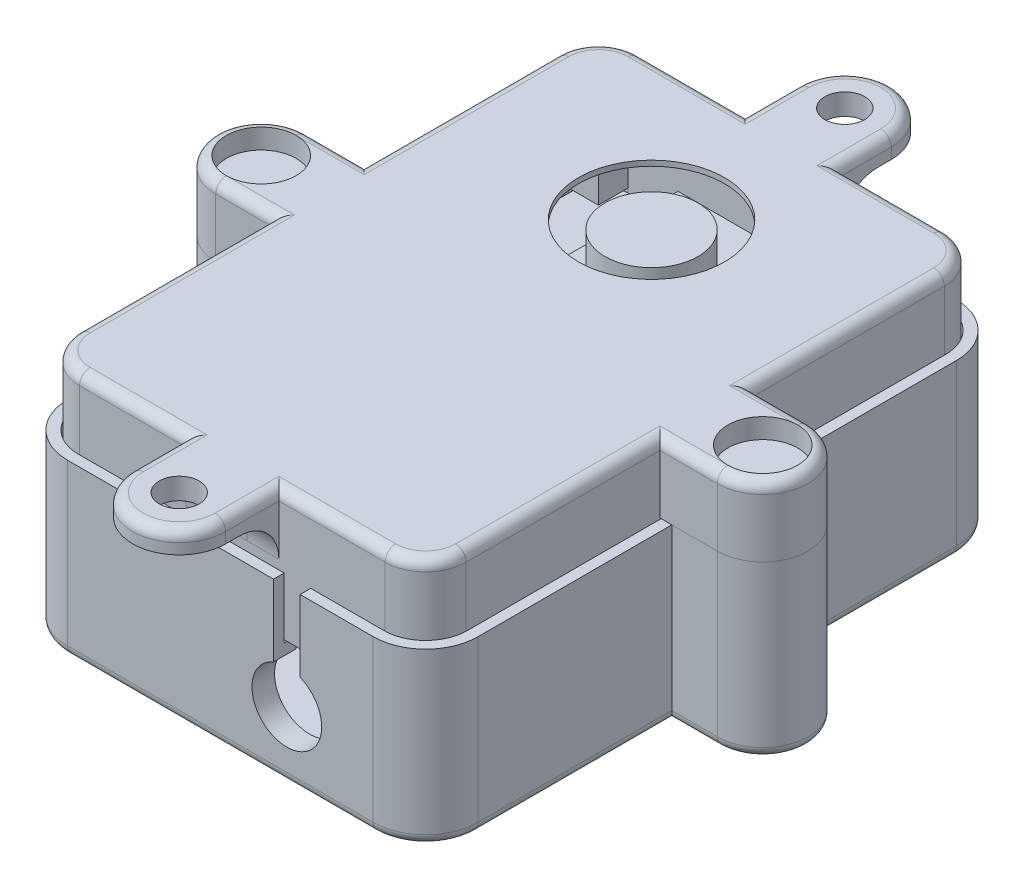
SolidWorks part; units mm, degrees
other "Front Lid"
other "ESP32 Cam"
other "Rear Lid"
ref_plane "Front Plane" through (0, 0, 0) normal (0, 0, 1) x (1, 0, 0)
ref_plane "Top Plane" through (0, 0, 0) normal (0, 1, 0) x (1, 0, 0)
ref_plane "Right Plane" through (0, 0, 0) normal (1, 0, 0) x (0, 0, -1)
sketch "Sketch1" plane through (0, 0, 0) normal (0, 1, 0) x (1, 0, 0)
  line L1 (-11.5, 20) -> (11.5, 20)
  line L2 (-13.5, 18) -> (-13.5, -18)
  line L3 (-11.5, -20) -> (11.5, -20)
  line L4 (13.5, 18) -> (13.5, -18)
  line L5 (-13.5, 20) -> (13.5, -20) construction
  line L6 (-13.5, -20) -> (13.5, 20) construction
  arc A0 (-11.5, 20) -> (-13.5, 18) centre (-11.5, 18) ccw
  arc A1 (11.5, 20) -> (13.5, 18) centre (11.5, 18) cw
  arc A2 (11.5, -20) -> (13.5, -18) centre (11.5, -18) ccw
  arc A3 (-13.5, -18) -> (-11.5, -20) centre (-11.5, -18) ccw
  point P0 (0, 0)
  dimension "D3" = 2
  dimension "D1" = 27
  dimension "D2" = 40
extrude "Boss-Extrude1" add sketch "Sketch1" along normal blind 1
sketch "Sketch2" plane through (0, 1, 0) normal (0, 1, 0) x (1, 0, 0)
  line L0 (0, 0) -> (0, 20) construction
  line L1 (11.5, 20) -> (-11.5, 20) construction
  line L3 (-7.5, 20) -> (7.5, 20)
  line L4 (-7.5, 20) -> (-7.5, 5)
  line L5 (-7.5, 5) -> (7.5, 5)
  line L6 (7.5, 20) -> (7.5, 5)
  line L7 (-7.5, 20) -> (7.5, 5) construction
  line L8 (-7.5, 5) -> (7.5, 20) construction
  point P5 (0, 12.5)
  dimension "D1" = 15
extrude "Boss-Extrude2" add sketch "Sketch2" along normal blind 2
sketch "Sketch3" plane through (0, 3, 0) normal (0, 1, 0) x (1, 0, 0)
  line L0 (0, 5) -> (0, 20) construction
  line L1 (-7.5, 5) -> (7.5, 5) construction
  line L2 (7.5, 20) -> (-7.5, 20) construction
  circle A0 centre (0, 10.5) radius 3.5
  dimension "D1" = 7
  dimension "D2" = 5.5
extrude "Lens Position" add sketch "Sketch3" along normal blind 6
sketch "Sketch5" plane through (0, 1, 0) normal (0, 1, 0) x (1, 0, 0)
  line L0 (-11.5, -20) -> (11.5, -20) construction
  line L1 (10, -8) -> (13, -8)
  line L2 (10, -8) -> (10, -11)
  line L3 (10, -11) -> (13, -11)
  line L4 (13, -8) -> (13, -11)
  line L5 (10, -8) -> (13, -11) construction
  line L6 (10, -11) -> (13, -8) construction
  line L7 (13.5, -18) -> (13.5, 18) construction
  point P0 (11.5, -9.5)
  dimension "D1" = 3
  dimension "D2" = 10.5
  dimension "D3" = 2
extrude "Boss-Extrude4" add sketch "Sketch5" along normal blind 1
sketch "Sketch6" plane through (0, 9, 0) normal (0, 1, 0) x (1, 0, 0)
  line L37 (7.5, 21.05) -> (-7.5, 21.05)
  line L38 (-7.5, 21.05) -> (-11.5, 21.05)
  line L39 (-14.55, 18) -> (-14.55, -18)
  line L40 (-11.5, -21.05) -> (11.5, -21.05)
  line L41 (14.55, -18) -> (14.55, 18)
  line L42 (11.5, 21.05) -> (7.5, 21.05)
  line L43 (7.5, 20.25) -> (-7.5, 20.25)
  line L44 (11.5, 20.25) -> (7.5, 20.25)
  line L45 (13.75, -18) -> (13.75, 18)
  line L46 (-11.5, -20.25) -> (11.5, -20.25)
  line L47 (-13.75, 18) -> (-13.75, -18)
  line L48 (-7.5, 20.25) -> (-11.5, 20.25)
  line L55 (7.5, 20.25) -> (-7.5, 20.25) construction
  line L56 (11.5, 20.25) -> (7.5, 20.25) construction
  line L57 (13.75, -18) -> (13.75, 18) construction
  line L58 (-11.5, -20.25) -> (11.5, -20.25) construction
  line L59 (-13.75, 18) -> (-13.75, -18) construction
  line L60 (-7.5, 20.25) -> (-11.5, 20.25) construction
  circle A6 centre (0, 10.5) radius 5.5
  circle A8 centre (0, 10.5) radius 5.5
  arc A36 (-11.5, 21.05) -> (-14.55, 18) centre (-11.5, 18) ccw
  arc A37 (-14.55, -18) -> (-11.5, -21.05) centre (-11.5, -18) ccw
  arc A38 (11.5, -21.05) -> (14.55, -18) centre (11.5, -18) ccw
  arc A39 (14.55, 18) -> (11.5, 21.05) centre (11.5, 18) ccw
  arc A40 (13.75, 18) -> (11.5, 20.25) centre (11.5, 18) ccw
  arc A41 (11.5, -20.25) -> (13.75, -18) centre (11.5, -18) ccw
  arc A42 (-13.75, -18) -> (-11.5, -20.25) centre (-11.5, -18) ccw
  arc A43 (-11.5, 20.25) -> (-13.75, 18) centre (-11.5, 18) ccw
  arc A44 (13.75, 18) -> (11.5, 20.25) centre (11.5, 18) ccw construction
  arc A45 (11.5, -20.25) -> (13.75, -18) centre (11.5, -18) ccw construction
  arc A46 (-13.75, -18) -> (-11.5, -20.25) centre (-11.5, -18) ccw construction
  arc A47 (-11.5, 20.25) -> (-13.75, 18) centre (-11.5, 18) ccw construction
  dimension "D1" = 0.25
  dimension "D2" = 0.8
  dimension "D3" = 2
extrude "Lens Opening" add sketch "Sketch6" along normal blind 0.4 from offset 0.25 separate body
sketch "Sketch8" plane through (0, 9.25, 0) normal (0, -1, 0) x (1, 0, 0)
  line L4 (-11.5, -21.05) -> (11.5, -21.05)
  line L5 (14.55, -18) -> (14.55, 18)
  line L6 (11.5, 21.05) -> (-11.5, 21.05)
  line L7 (-14.55, 18) -> (-14.55, -18)
  line L8 (-11.5, -21.05) -> (11.5, -21.05)
  line L9 (14.55, -18) -> (14.55, 18)
  line L10 (11.5, 21.05) -> (-11.5, 21.05)
  line L11 (-14.55, 18) -> (-14.55, -18)
  line L16 (-11.5, -20.25) -> (11.5, -20.25)
  line L17 (13.75, -18) -> (13.75, 18)
  line L18 (11.5, 20.25) -> (-11.5, 20.25)
  line L19 (-13.75, 18) -> (-13.75, -18)
  line L20 (-11.5, -20.25) -> (11.5, -20.25)
  line L21 (13.75, -18) -> (13.75, 18)
  line L22 (11.5, 20.25) -> (-11.5, 20.25)
  line L23 (-13.75, 18) -> (-13.75, -18)
  arc A4 (11.5, -21.05) -> (14.55, -18) centre (11.5, -18) ccw
  arc A5 (14.55, 18) -> (11.5, 21.05) centre (11.5, 18) ccw
  arc A6 (-11.5, 21.05) -> (-14.55, 18) centre (-11.5, 18) ccw
  arc A7 (-14.55, -18) -> (-11.5, -21.05) centre (-11.5, -18) ccw
  arc A8 (11.5, -21.05) -> (14.55, -18) centre (11.5, -18) ccw
  arc A9 (14.55, 18) -> (11.5, 21.05) centre (11.5, 18) ccw
  arc A10 (-11.5, 21.05) -> (-14.55, 18) centre (-11.5, 18) ccw
  arc A11 (-14.55, -18) -> (-11.5, -21.05) centre (-11.5, -18) ccw
  arc A16 (11.5, -20.25) -> (13.75, -18) centre (11.5, -18) ccw
  arc A17 (13.75, 18) -> (11.5, 20.25) centre (11.5, 18) ccw
  arc A18 (-11.5, 20.25) -> (-13.75, 18) centre (-11.5, 18) ccw
  arc A19 (-13.75, -18) -> (-11.5, -20.25) centre (-11.5, -18) ccw
  arc A20 (11.5, -20.25) -> (13.75, -18) centre (11.5, -18) ccw
  arc A21 (13.75, 18) -> (11.5, 20.25) centre (11.5, 18) ccw
  arc A22 (-11.5, 20.25) -> (-13.75, 18) centre (-11.5, 18) ccw
  arc A23 (-13.75, -18) -> (-11.5, -20.25) centre (-11.5, -18) ccw
  dimension "D1" = 0
  dimension "D2" = 0.8
extrude "Boss-Extrude7" add sketch "Sketch8" along normal up to vertex (9.25 mm away) up to point (-11.5, 0, 20)
sketch "Sketch9" plane through (0, 9.25, 0) normal (0, -1, 0) x (1, 0, 0)
  line L0 (13.75, 18) -> (11.5, 18)
  line L1 (11.5, 18) -> (11.5, 20.25)
  line L2 (4.95, 0) -> (-4.95, 0) construction
  line L3 (11.5, -18) -> (11.5, -20.25)
  line L4 (13.75, -18) -> (11.5, -18)
  line L5 (0, -4.95) -> (0, 4.95) construction
  line L6 (-13.75, -18) -> (-11.5, -18)
  line L7 (-11.5, -18) -> (-11.5, -20.25)
  line L8 (-11.5, 18) -> (-11.5, 20.25)
  line L9 (-13.75, 18) -> (-11.5, 18)
  arc A0 (13.75, 18) -> (11.5, 20.25) centre (11.5, 18) ccw construction
  arc A1 (13.75, 18) -> (11.5, 20.25) centre (11.5, 18) ccw
  arc A2 (13.75, -18) -> (11.5, -20.25) centre (11.5, -18) cw
  arc A3 (-13.75, -18) -> (-11.5, -20.25) centre (-11.5, -18) ccw
  arc A4 (-13.75, 18) -> (-11.5, 20.25) centre (-11.5, 18) cw
extrude "Boss-Extrude9" add sketch "Sketch9" along normal offset from surface (8.15 mm away) 0.1 up to face at (0, 1, -4.1667)
sketch "Sketch11" plane through (0, 9.65, 0) normal (0, 1, 0) x (1, 0, 0)
  line L1 (13.75, -7.6) -> (9.6, -7.6)
  line L2 (9.6, -7.6) -> (9.6, -11.4)
  line L3 (9.6, -11.4) -> (13.75, -11.4)
  line L4 (13, -11) -> (13, -8)
  line L5 (13, -8) -> (10, -8)
  line L6 (10, -8) -> (10, -11)
  line L7 (10, -11) -> (13, -11)
  line L8 (13, -11) -> (13, -8) construction
  line L9 (13, -8) -> (10, -8) construction
  line L10 (10, -8) -> (10, -11) construction
  line L11 (10, -11) -> (13, -11) construction
  line L12 (13.75, 18) -> (13.75, -18) construction
  line L13 (13.75, -7.6) -> (13.75, -11.4)
  line L14 (9.6, -11.4) -> (13.4, -11.4) construction
  line L15 (13.4, -11.4) -> (13.4, -7.6) construction
  line L16 (13.4, -7.6) -> (9.6, -7.6) construction
  dimension "D1" = 0
  dimension "D2" = 0.4
extrude "Cut-Extrude1" [suppressed] cut sketch "Sketch11" against normal up to vertex
sketch "Sketch12" plane through (0, 0, 0) normal (0, -1, 0) x (1, 0, 0)
  line L0 (0, 0) -> (0, 20) construction
  line L1 (-11.5, 20) -> (11.5, 20) construction
  line L3 (9.375, -5.65) -> (-9.375, -5.65)
  line L4 (9.375, -5.65) -> (9.375, 20)
  line L5 (9.375, 20) -> (-9.375, 20)
  line L6 (-9.375, -5.65) -> (-9.375, 20)
  line L7 (9.375, -5.65) -> (-9.375, 20) construction
  line L8 (9.375, 20) -> (-9.375, -5.65) construction
  point P5 (0, 7.175)
  dimension "D1" = 18.75
  dimension "D2" = 25.65
extrude "Boss-Extrude10" add sketch "Sketch12" along normal blind 0.75
sketch "Sketch13" plane through (0, -0.75, 0) normal (0, -1, 0) x (1, 0, 0)
  line L0 (0, -5.65) -> (0, 20) construction
  line L1 (-9.375, -5.65) -> (9.375, -5.65) construction
  line L2 (8, 12.35) -> (2, 12.35) construction
  line L3 (2, 12.35) -> (-8, 12.35)
  line L4 (8, 9.35) -> (8, -5.15)
  line L5 (8, -5.15) -> (-8, -5.15)
  line L6 (-8, 12.35) -> (-8, -5.15)
  line L7 (8, 12.35) -> (-8, -5.15) construction
  line L8 (8, -5.15) -> (-8, 12.35) construction
  line L11 (8, 9.35) -> (2, 9.35)
  line L12 (2, 12.35) -> (2, 9.35)
  line L13 (8, 12.35) -> (8, 9.35) construction
  line L14 (9.375, 20) -> (11.5, 20) construction
  point P5 (0, 3.6)
  dimension "D1" = 16
  dimension "D2" = 17.5
  dimension "D3" = 3
  dimension "D4" = 6
  dimension "D5" = 0.5
extrude "Boss-Extrude11" add sketch "Sketch13" along normal blind 2.3
sketch "Sketch14" plane through (0, 0, 0) normal (0, -1, 0) x (1, 0, 0)
  line L0 (9.375, 20) -> (11.5, 20) construction
  line L1 (12.75, -16.2) -> (10.25, -16.2)
  line L2 (12.75, -16.2) -> (12.75, 4)
  line L3 (12.75, 4) -> (10.25, 4)
  line L4 (10.25, -16.2) -> (10.25, 4)
  line L5 (12.75, -16.2) -> (10.25, 4) construction
  line L6 (12.75, 4) -> (10.25, -16.2) construction
  line L7 (13.5, 18) -> (13.5, -18) construction
  point P0 (11.5, -6.1)
  dimension "D1" = 20.2
  dimension "D2" = 2.5
  dimension "D3" = 16
  dimension "D4" = 0.75
extrude "Boss-Extrude12" add sketch "Sketch14" along normal blind 2.45
sketch "Sketch16" plane through (0, -2.45, 0) normal (0, -1, 0) x (1, 0, 0)
  line L0 (11.5, 4) -> (11.5, -16.2) construction
  line L3 (11.2, 3) -> (11.8, 3)
  line L8 (11.2, 3) -> (11.2, 2.4)
  line L9 (11.2, 2.4) -> (11.8, 2.4)
  line L10 (11.8, 3) -> (11.8, 2.4)
  line L11 (12.75, 4) -> (10.25, 4) construction
  line L12 (10.25, -16.2) -> (12.75, -16.2) construction
  dimension "D1" = 0.6
  dimension "D2" = 1
extrude "Boss-Extrude14" add sketch "Sketch16" along normal blind 5.5
pattern_linear "LPattern1" count 8 spacing 2.5 along (0, 0, -1) of "Boss-Extrude14"
sketch "Sketch17" plane through (0, -3.05, 0) normal (0, -1, 0) x (1, 0, 0)
  line L14 (-11.5, -21.95) -> (11.5, -21.95)
  line L15 (15.45, -18) -> (15.45, 18)
  line L16 (-11.5, -21.15) -> (11.5, -21.15)
  line L17 (-14.65, 18) -> (-14.65, -18)
  line L18 (11.5, 21.15) -> (-11.5, 21.15)
  line L19 (-11.5, -21.15) -> (11.5, -21.15)
  line L20 (-14.65, 18) -> (-14.65, -18)
  line L21 (11.5, 21.15) -> (-11.5, 21.15)
  line L22 (14.65, -18) -> (14.65, 18)
  line L23 (11.5, 21.95) -> (-11.5, 21.95)
  line L24 (-15.45, 18) -> (-15.45, -18)
  arc A16 (11.5, -21.95) -> (15.45, -18) centre (11.5, -18) ccw
  arc A17 (15.45, 18) -> (11.5, 21.95) centre (11.5, 18) ccw
  arc A18 (-11.5, 21.95) -> (-15.45, 18) centre (-11.5, 18) ccw
  arc A19 (-15.45, -18) -> (-11.5, -21.95) centre (-11.5, -18) ccw
  arc A20 (11.5, -21.15) -> (14.65, -18) centre (11.5, -18) ccw
  arc A21 (-14.65, -18) -> (-11.5, -21.15) centre (-11.5, -18) ccw
  arc A22 (-11.5, 21.15) -> (-14.65, 18) centre (-11.5, 18) ccw
  arc A23 (14.65, 18) -> (11.5, 21.15) centre (11.5, 18) ccw
  arc A24 (11.5, -21.15) -> (14.65, -18) centre (11.5, -18) ccw
  arc A25 (-14.65, -18) -> (-11.5, -21.15) centre (-11.5, -18) ccw
  arc A26 (-11.5, 21.15) -> (-14.65, 18) centre (-11.5, 18) ccw
  arc A27 (14.65, 18) -> (11.5, 21.15) centre (11.5, 18) ccw
  dimension "D1" = 0.1
  dimension "D2" = 0.8
extrude "Boss-Extrude15" add sketch "Sketch17" against normal blind 12.5 from offset 5 separate body
sketch "Sketch18" plane through (0, -8.05, 0) normal (0, -1, 0) x (1, 0, 0)
  line L0 (-11.5, -20.25) -> (11.5, -20.25) construction
  line L1 (-13.75, 18) -> (-13.75, -18) construction
  line L2 (13.75, -18) -> (13.75, 18) construction
  line L3 (11.5, 20.25) -> (-11.5, 20.25) construction
  line L4 (-11.5, -20.25) -> (11.5, -20.25)
  line L5 (-13.75, 18) -> (-13.75, -18)
  line L6 (13.75, -18) -> (13.75, 18)
  line L7 (11.5, 20.25) -> (-11.5, 20.25)
  line L8 (-11.5, -21.15) -> (11.5, -21.15) construction
  line L9 (-14.65, 18) -> (-14.65, -18) construction
  line L10 (11.5, 21.15) -> (-11.5, 21.15) construction
  line L11 (14.65, -18) -> (14.65, 18) construction
  line L12 (-11.5, -21.15) -> (11.5, -21.15)
  line L13 (-14.65, 18) -> (-14.65, -18)
  line L14 (11.5, 21.15) -> (-11.5, 21.15)
  line L15 (14.65, -18) -> (14.65, 18)
  arc A0 (11.5, -20.25) -> (13.75, -18) centre (11.5, -18) ccw construction
  arc A1 (-13.75, -18) -> (-11.5, -20.25) centre (-11.5, -18) ccw construction
  arc A2 (-11.5, 20.25) -> (-13.75, 18) centre (-11.5, 18) ccw construction
  arc A3 (13.75, 18) -> (11.5, 20.25) centre (11.5, 18) ccw construction
  arc A4 (11.5, -20.25) -> (13.75, -18) centre (11.5, -18) ccw
  arc A5 (-13.75, -18) -> (-11.5, -20.25) centre (-11.5, -18) ccw
  arc A6 (-11.5, 20.25) -> (-13.75, 18) centre (-11.5, 18) ccw
  arc A7 (13.75, 18) -> (11.5, 20.25) centre (11.5, 18) ccw
  arc A8 (11.5, -21.15) -> (14.65, -18) centre (11.5, -18) ccw construction
  arc A9 (-14.65, -18) -> (-11.5, -21.15) centre (-11.5, -18) ccw construction
  arc A10 (-11.5, 21.15) -> (-14.65, 18) centre (-11.5, 18) ccw construction
  arc A11 (14.65, 18) -> (11.5, 21.15) centre (11.5, 18) ccw construction
  arc A12 (11.5, -21.15) -> (14.65, -18) centre (11.5, -18) ccw
  arc A13 (-14.65, -18) -> (-11.5, -21.15) centre (-11.5, -18) ccw
  arc A14 (-11.5, 21.15) -> (-14.65, 18) centre (-11.5, 18) ccw
  arc A15 (14.65, 18) -> (11.5, 21.15) centre (11.5, 18) ccw
extrude "Boss-Extrude16" add sketch "Sketch18" against normal offset from surface (7.95 mm away) 0.1 up to face at (0, 0, 0)
sketch "Sketch19" plane through (0, -8.05, 0) normal (0, -1, 0) x (1, 0, 0)
  line L165 (0, -9.955) -> (0, 9.955) construction
  line L166 (-13.25, -16.7) -> (-13.25, 4.5)
  line L167 (-13.25, 4.5) -> (-9.75, 4.5)
  line L168 (-9.75, 4.5) -> (-9.75, -16.7)
  line L169 (13.25, 4.5) -> (9.75, 4.5)
  line L170 (13.25, -16.7) -> (13.25, 4.5)
  line L171 (9.75, -16.7) -> (13.25, -16.7)
  line L172 (9.75, 4.5) -> (9.75, -16.7)
  line L173 (13.25, 4.5) -> (9.75, 4.5)
  line L174 (13.25, -16.7) -> (13.25, 4.5)
  line L175 (9.75, -16.7) -> (13.25, -16.7)
  line L176 (9.75, 4.5) -> (9.75, -16.7)
  line L177 (-9.75, -16.7) -> (-13.25, -16.7)
  line L178 (11.5, 21.95) -> (-11.5, 21.95) construction
  line L179 (-15.45, 18) -> (-15.45, -18) construction
  line L180 (-11.5, -21.95) -> (11.5, -21.95) construction
  line L181 (15.45, -18) -> (15.45, 18) construction
  line L182 (11.5, 21.95) -> (-11.5, 21.95)
  line L183 (-15.45, 18) -> (-15.45, -18)
  line L184 (-11.5, -21.95) -> (11.5, -21.95)
  line L185 (15.45, -18) -> (15.45, 18)
  arc A0 (15.45, 18) -> (11.5, 21.95) centre (11.5, 18) ccw construction
  arc A1 (-11.5, 21.95) -> (-15.45, 18) centre (-11.5, 18) ccw construction
  arc A2 (-15.45, -18) -> (-11.5, -21.95) centre (-11.5, -18) ccw construction
  arc A3 (11.5, -21.95) -> (15.45, -18) centre (11.5, -18) ccw construction
  arc A4 (15.45, 18) -> (11.5, 21.95) centre (11.5, 18) ccw
  arc A5 (-11.5, 21.95) -> (-15.45, 18) centre (-11.5, 18) ccw
  arc A6 (-15.45, -18) -> (-11.5, -21.95) centre (-11.5, -18) ccw
  arc A7 (11.5, -21.95) -> (15.45, -18) centre (11.5, -18) ccw
  dimension "D1" = 0.5
extrude "Boss-Extrude17" add sketch "Sketch19" along normal blind 0.4
sketch "Sketch20" plane through (0, 0, 21.95) normal (0, 0, 1) x (1, 0, 0)
  line L0 (2, -3.05) -> (2, -0.75) construction
  line L1 (8, -0.75) -> (2, -0.75) construction
  line L2 (8, -3.05) -> (8, -0.75) construction
  line L3 (8, -3.05) -> (2, -3.05) construction
  line L4 (2, -3.05) -> (2, -0.75) construction
  line L5 (8, -0.75) -> (2, -0.75) construction
  line L6 (8, -3.05) -> (8, -0.75) construction
  line L7 (8, -3.05) -> (2, -3.05) construction
  line L8 (8, -3.05) -> (2, -0.75) construction
  line L9 (8, -0.75) -> (2, -3.05) construction
  line L10 (5, -1.9) -> (5, -3.375) construction
  line L12 (9.375, -0.75) -> (-9.375, -0.75) construction
  line L13 (9.375, -0.75) -> (-9.375, -0.75) construction
  circle A0 centre (5, -3.375) radius 2.625
  dimension "D1" = 5.25
extrude "Cut-Extrude2" cut sketch "Sketch20" against normal up to next (1.7 mm away) contours A0
sketch "Sketch22" plane through (0, -8.05, 0) normal (0, 1, 0) x (1, 0, 0)
  line L0 (13.75, -18) -> (11.5, -18)
  line L1 (11.5, -18) -> (11.5, -20.25)
  line L2 (-9.955, 0) -> (9.955, 0) construction
  line L3 (11.5, 18) -> (11.5, 20.25)
  line L4 (13.75, 18) -> (11.5, 18)
  line L5 (0, -9.955) -> (0, 9.955) construction
  line L6 (-13.75, 18) -> (-11.5, 18)
  line L7 (-11.5, 18) -> (-11.5, 20.25)
  line L8 (-11.5, -18) -> (-11.5, -20.25)
  line L9 (-13.75, -18) -> (-11.5, -18)
  arc A0 (11.5, -20.25) -> (13.75, -18) centre (11.5, -18) ccw construction
  arc A1 (11.5, -20.25) -> (13.75, -18) centre (11.5, -18) ccw
  arc A2 (11.5, 20.25) -> (13.75, 18) centre (11.5, 18) cw
  arc A3 (-11.5, 20.25) -> (-13.75, 18) centre (-11.5, 18) ccw
  arc A4 (-11.5, -20.25) -> (-13.75, -18) centre (-11.5, -18) cw
extrude "Boss-Extrude18" add sketch "Sketch22" along normal up to vertex (6.05 mm away)
sketch "Sketch23" [suppressed] plane through (0, 9.25, 0) normal (0, -1, 0) x (1, 0, 0)
  line L1 (9.6, 11.4) -> (13.75, 11.4) construction
  line L2 (9.6, 7.6) -> (9.6, 11.4) construction
  line L3 (13.75, 7.6) -> (9.6, 7.6) construction
  line L5 (9.6, 11.4) -> (13.75, 11.4)
  line L6 (9.6, 7.6) -> (9.6, 11.4)
  line L7 (13.75, 7.6) -> (9.6, 7.6)
  line L8 (13.75, 6.8) -> (8.8, 6.8)
  line L9 (8.8, 6.8) -> (8.8, 12.2)
  line L10 (8.8, 12.2) -> (13.75, 12.2)
  line L11 (13.75, 7.6) -> (13.75, 6.8)
  line L12 (13.75, 12.2) -> (13.75, 11.4)
  dimension "D1" = 0.8
extrude "Boss-Extrude19" [suppressed] add sketch "Sketch23" along normal offset from surface (7.15 mm away) 1
mirror "Mirror1" about plane through (0, 0, 0) normal (1, 0, 0) of "LPattern1", "Boss-Extrude12", "Boss-Extrude14"
sketch "Sketch24" plane through (0, 9.65, 0) normal (0, 1, 0) x (1, 0, 0)
  line L0 (0, 0) -> (0, 25.05) construction
  line L2 (-3.5, 25.05) -> (-3.5, 21.05)
  line L8 (11.5, 21.05) -> (-11.5, 21.05) construction
  line L9 (3.5, 25.05) -> (3.5, 21.05)
  line L10 (-3.5, 21.05) -> (3.5, 21.05)
  line L11 (-9.955, 0) -> (9.955, 0) construction
  line L12 (-3.5, -21.05) -> (3.5, -21.05)
  line L13 (3.5, -25.05) -> (3.5, -21.05)
  line L14 (-3.5, -25.05) -> (-3.5, -21.05)
  circle A1 centre (0, 25.05) radius 1.5
  arc A2 (3.5, 25.05) -> (-3.5, 25.05) centre (0, 25.05) ccw
  circle A3 centre (0, 25.05) radius 3.5 construction
  arc A4 (3.5, -25.05) -> (-3.5, -25.05) centre (0, -25.05) cw
  circle A5 centre (0, -25.05) radius 1.5
  dimension "D2" = 3
  dimension "D1" = 2
extrude "Boss-Extrude20" add sketch "Sketch24" against normal blind 1.6
sketch "Sketch25" plane through (0, -8.45, 0) normal (0, -1, 0) x (1, 0, 0)
  line L0 (15.45, 0) -> (18.875, 0) construction
  line L1 (15.45, -18) -> (15.45, 18) construction
  line L2 (18.875, 3.425) -> (15.45, 3.425)
  line L3 (18.875, -3.425) -> (15.45, -3.425)
  line L4 (15.45, -3.425) -> (15.45, 0)
  line L5 (15.45, 0) -> (15.45, 3.425)
  line L6 (0, -9.955) -> (0, 9.955) construction
  line L7 (-15.45, 0) -> (-18.875, 0) construction
  line L8 (-15.45, 0) -> (-15.45, 3.425)
  line L9 (-15.45, -3.425) -> (-15.45, 0)
  line L10 (-18.875, -3.425) -> (-15.45, -3.425)
  line L11 (-18.875, 3.425) -> (-15.45, 3.425)
  circle A0 centre (18.875, 0) radius 2.625 construction
  arc A1 (18.875, -3.425) -> (18.875, 3.425) centre (18.875, 0) ccw
  circle A2 centre (18.875, 0) radius 3.425 construction
  circle A3 centre (-18.875, 0) radius 2.625 construction
  arc A4 (-18.875, -3.425) -> (-18.875, 3.425) centre (-18.875, 0) cw
  dimension "D1" = 5.25
  dimension "D2" = 0.8
extrude "Boss-Extrude21" add sketch "Sketch25" against normal up to vertex (12.9 mm away) up to point (15.45, 4.45, 18)
sketch "Sketch26" plane through (0, 9.65, 0) normal (0, 1, 0) x (1, 0, 0)
  line L0 (15.45, 3.425) -> (18.875, 3.425) construction
  line L1 (18.875, -3.425) -> (15.45, -3.425) construction
  line L2 (15.45, 3.425) -> (18.875, 3.425)
  line L3 (18.875, -3.425) -> (15.45, -3.425)
  line L4 (15.45, 3.425) -> (14.55, 3.425)
  line L5 (14.55, -18) -> (14.55, 18) construction
  line L6 (14.55, 3.425) -> (14.55, -3.425)
  line L7 (14.55, -3.425) -> (15.45, -3.425)
  line L8 (0, -9.955) -> (0, 9.955) construction
  line L9 (-14.55, -3.425) -> (-15.45, -3.425)
  line L10 (-14.55, 3.425) -> (-14.55, -3.425)
  line L11 (-15.45, 3.425) -> (-14.55, 3.425)
  line L12 (-18.875, -3.425) -> (-15.45, -3.425)
  line L13 (-15.45, 3.425) -> (-18.875, 3.425)
  arc A0 (18.875, -3.425) -> (18.875, 3.425) centre (18.875, 0) ccw construction
  arc A1 (18.875, -3.425) -> (18.875, 3.425) centre (18.875, 0) ccw
  arc A2 (-18.875, -3.425) -> (-18.875, 3.425) centre (-18.875, 0) cw
extrude "Boss-Extrude22" add sketch "Sketch26" against normal up to vertex (5.2 mm away) up to point (15.45, 4.45, 3.425)
sketch "Sketch27" plane through (0, 4.45, 0) normal (0, 1, 0) x (1, 0, 0)
  line L0 (0, -9.955) -> (0, 9.955) construction
  circle A0 centre (18.875, 0) radius 2.625 construction
  circle A1 centre (18.875, 0) radius 2.625
  circle A2 centre (-18.875, 0) radius 2.625
extrude "Magnet Hole" cut sketch "Sketch27" against normal mid plane 2.5
sketch "Sketch28" plane through (0, 9.65, 0) normal (0, 1, 0) x (1, 0, 0)
  line L0 (0, -9.955) -> (0, 9.955) construction
  circle A0 centre (18.875, 0) radius 2.625 construction
  circle A1 centre (18.875, 0) radius 2.625
  circle A2 centre (-18.875, 0) radius 2.625
extrude "Cut-Extrude3" cut sketch "Sketch28" against normal blind 1.5
sketch "Sketch29" plane through (0, -8.45, 0) normal (0, -1, 0) x (1, 0, 0)
  line L0 (0, -9.955) -> (0, 9.955) construction
  circle A0 centre (18.875, 0) radius 2.625 construction
  circle A1 centre (18.875, 0) radius 2.625
  circle A2 centre (-18.875, 0) radius 2.625
extrude "Cut-Extrude4" cut sketch "Sketch29" against normal blind 1.5
fillet "Fillet2" radius 0.8 16 edges at (-14.2931, -8.45, -20.7931) (-15.45, -8.45, 10.7125) (-15.45, -8.45, -10.7125) (-14.2931, -8.45, 20.7931) (0, -8.45, 21.95) (14.2931, -8.45, 20.7931) (15.45, -8.45, -10.7125) (15.45, -8.45, 10.7125) (14.2931, -8.45, -20.7931) (0, -8.45, -21.95) (17.1625, -8.45, -3.425) (17.1625, -8.45, 3.425) (22.3, -8.45, 0) (-17.1625, -8.45, 3.425) (-17.1625, -8.45, -3.425) (-22.3, -8.45, 0)
fillet "Fillet4" radius 3 2 edges at (0, 8.05, -21.05) (0, 8.05, 21.05)
fillet "Fillet6" radius 0.8 24 edges at (16.7125, 9.65, -3.425) (22.3, 9.65, 0) (14.55, 9.65, -10.7125) (13.6567, 9.65, -20.1567) (-14.55, 9.65, -10.7125) (-13.6567, 9.65, -20.1567) (3.5, 9.65, -23.05) (-3.5, 9.65, -23.05) (-3.5, 9.65, 23.05) (3.5, 9.65, 23.05) (-14.55, 9.65, 10.7125) (-7.5, 9.65, 21.05) (7.5, 9.65, 21.05) (14.55, 9.65, 10.7125) (-16.7125, 9.65, 3.425) (-22.3, 9.65, 0) (16.7125, 9.65, 3.425) (7.5, 9.65, -21.05) (-7.5, 9.65, -21.05) (0, 9.65, -28.55) (0, 9.65, 28.55) (-13.6567, 9.65, 20.1567) (13.6567, 9.65, 20.1567) (-16.7125, 9.65, -3.425)
sketch "Sketch30" plane through (0, 0, 21.95) normal (0, 0, 1) x (1, 0, 0)
  line L0 (5, -3.375) -> (5, 4.45) construction
  line L1 (11.5, 4.45) -> (-11.5, 4.45) construction
  line L2 (6, 4.45) -> (6, -0.9479)
  line L3 (4, 4.45) -> (4, -0.9479)
  line L4 (4, 4.45) -> (6, 4.45)
  circle A0 centre (5, -3.375) radius 2.625 construction
  arc A1 (6, -0.9479) -> (4, -0.9479) centre (5, -3.375) ccw
  dimension "D1" = 2
extrude "Cut-Extrude5" cut sketch "Sketch30" against normal up to next (1.7 mm away)
